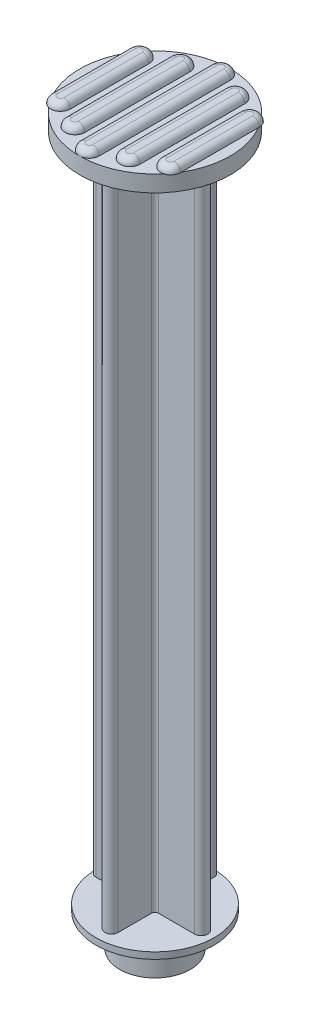
SolidWorks part; units mm, degrees
ref_plane "Plan de face" through (0, 0, 0) normal (0, 0, 1) x (1, 0, 0)
ref_plane "Plan de dessus" through (0, 0, 0) normal (0, 1, 0) x (1, 0, 0)
ref_plane "Plan de droite" through (0, 0, 0) normal (1, 0, 0) x (0, 0, -1)
sketch "Esquisse1" plane through (0, 0, 0) normal (0, 0, 1) x (1, 0, 0)
  line L0 (0, 0) -> (0, 6)
  line L1 (0, 6) -> (9, 6)
  line L2 (9, 6) -> (9, 5)
  line L3 (9, 5) -> (6, 5)
  line L4 (6, 5) -> (6, 3)
  line L5 (6, 3) -> (5.4, 3)
  line L6 (5.4, 3) -> (5.4, 0)
  line L7 (5.4, 0) -> (0, 0)
  dimension "D1" = 9
  dimension "D2" = 1
  dimension "D3" = 2
  dimension "D4" = 3
  dimension "D5" = 5.4
  dimension "D6" = 6
revolve "Révolution1" add sketch "Esquisse1" angle 360 about L0
sketch "Esquisse2" plane through (0, 6, 0) normal (0, 1, 0) x (1, 0, 0)
  line L0 (-8, 0) -> (7.041, 0) construction
  line L1 (-8.0046, 1) -> (-1.5, 1)
  line L2 (-8.0046, -1) -> (-1.5, -1)
  line L3 (0, 8) -> (0, -6.6345) construction
  line L4 (1, 8) -> (1, 1.5)
  line L5 (-1, 8) -> (-1, 1.5)
  line L6 (1.5, 1) -> (7.0463, 1)
  line L7 (1.5, -1) -> (7.0358, -1)
  line L8 (-1, -1.5) -> (-1, -6.6345)
  line L9 (1, -1.5) -> (1, -6.6345)
  arc A0 (-8.0046, 1) -> (-8.0046, -1) centre (-8, 0) ccw
  arc A1 (7.0358, -1) -> (7.0463, 1) centre (7.041, 0) ccw
  arc A2 (1, 8) -> (-1, 8) centre (0, 8) ccw
  arc A3 (-1, -6.6345) -> (1, -6.6345) centre (0, -6.6345) ccw
  arc A4 (-1, -1.5) -> (-1.5, -1) centre (-1.5, -1.5) ccw
  arc A5 (1, -1.5) -> (1.5, -1) centre (1.5, -1.5) cw
  arc A6 (1.5, 1) -> (1, 1.5) centre (1.5, 1.5) cw
  arc A7 (-1.5, 1) -> (-1, 1.5) centre (-1.5, 1.5) ccw
  point P3 (0, 0)
  point P8 (0.1449, 0.5791)
  point P22 (-1, -1)
  point P25 (1, -1)
  dimension "D3" = 1
  dimension "D8" = 1
  dimension "D9" = 1
  dimension "D10" = 1
  dimension "D11" = 0.5
  dimension "D1" = 8
  dimension "D2" = 8
  dimension "D4" = 1
  dimension "D5" = 1
  dimension "D6" = 1
  dimension "D7" = 1
extrude "Boss.-Extru.1" add sketch "Esquisse2" along normal blind 102
sketch "Esquisse4" plane through (0, 108, 0) normal (0, 1, 0) x (1, 0, 0)
  circle A0 centre (0, 0) radius 11.5
  dimension "D1" = 23
extrude "Boss.-Extru.2" add sketch "Esquisse4" along normal blind 2.5
sketch "Esquisse5" plane through (0, 110.5, 0) normal (0, 1, 0) x (1, 0, 0)
  line L0 (0, -11.5) -> (0, 11.5) construction
  line L1 (-11.5, 0) -> (11.5, 0) construction
  line L2 (0, -10) -> (0, 10) construction
  line L3 (-1.5, -10) -> (-1.5, 10)
  line L4 (1.5, -10) -> (1.5, 10)
  line L5 (-4.2, -8) -> (-4.2, 8) construction
  line L6 (-5.7, -8) -> (-5.7, 8)
  line L7 (-2.7, -8) -> (-2.7, 8)
  line L8 (-8.4, -6) -> (-8.4, 6) construction
  line L9 (-9.9, -6) -> (-9.9, 6)
  line L10 (-6.9, -6) -> (-6.9, 6)
  line L11 (8.4, -6) -> (8.4, 6) construction
  line L12 (9.9, -6) -> (9.9, 6)
  line L13 (6.9, -6) -> (6.9, 6)
  line L14 (4.2, -8) -> (4.2, 8) construction
  line L15 (5.7, -8) -> (5.7, 8)
  line L16 (2.7, -8) -> (2.7, 8)
  circle A0 centre (0, 0) radius 11.5 construction
  arc A1 (-1.5, -10) -> (1.5, -10) centre (0, -10) ccw
  arc A2 (1.5, 10) -> (-1.5, 10) centre (0, 10) ccw
  arc A3 (-5.7, -8) -> (-2.7, -8) centre (-4.2, -8) ccw
  arc A4 (-2.7, 8) -> (-5.7, 8) centre (-4.2, 8) ccw
  arc A5 (-9.9, -6) -> (-6.9, -6) centre (-8.4, -6) ccw
  arc A6 (-6.9, 6) -> (-9.9, 6) centre (-8.4, 6) ccw
  arc A7 (9.9, -6) -> (6.9, -6) centre (8.4, -6) cw
  arc A8 (6.9, 6) -> (9.9, 6) centre (8.4, 6) cw
  arc A9 (5.7, -8) -> (2.7, -8) centre (4.2, -8) cw
  arc A10 (2.7, 8) -> (5.7, 8) centre (4.2, 8) cw
  point P10 (0, 0)
  point P15 (-4.2, 0)
  point P24 (-8.4, 0)
  point P34 (8.4, 0)
  point P41 (4.2, 0)
  dimension "D6" = 1.5
  dimension "D7" = 1.5
  dimension "D8" = 1.5
  dimension "D1" = 10
  dimension "D2" = 6
  dimension "D3" = 8
  dimension "D4" = 4.2
  dimension "D5" = 4.2
extrude "Boss.-Extru.3" add sketch "Esquisse5" along normal blind 1
fillet "Congé1" radius 1 20 edges at (-9.9, 111.5, 0) (-8.4, 111.5, -7.5) (-6.9, 111.5, 0) (-8.4, 111.5, 7.5) (-5.7, 111.5, 0) (-4.2, 111.5, -9.5) (-2.7, 111.5, 0) (-4.2, 111.5, 9.5) (-1.5, 111.5, 0) (0, 111.5, -11.5) (1.5, 111.5, 0) (0, 111.5, 11.5) (2.7, 111.5, 0) (4.2, 111.5, -9.5) (5.7, 111.5, 0) (4.2, 111.5, 9.5) (6.9, 111.5, 0) (8.4, 111.5, -7.5) (9.9, 111.5, 0) (8.4, 111.5, 7.5)
